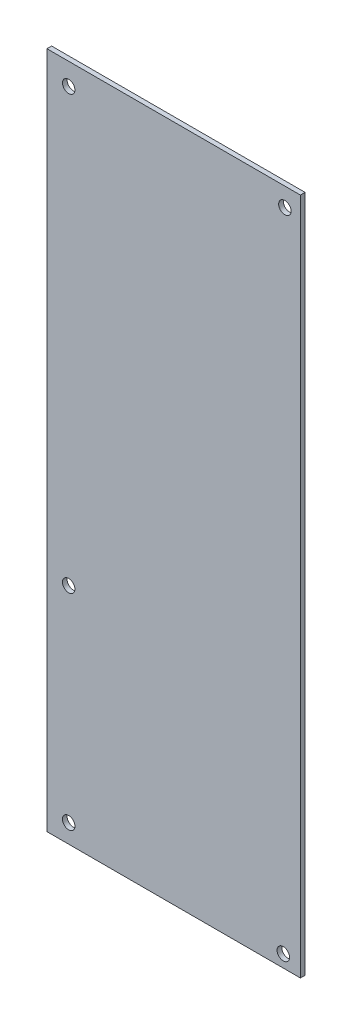
SolidWorks part; units mm, degrees
ref_plane "Plan de face" through (0, 0, 0) normal (0, 0, 1) x (1, 0, 0)
ref_plane "Plan de dessus" through (0, 0, 0) normal (0, 1, 0) x (1, 0, 0)
ref_plane "Plan de droite" through (0, 0, 0) normal (1, 0, 0) x (0, 0, -1)
sketch "Main-Sketch" plane through (0, 0, 0) normal (0, 0, 1) x (1, 0, 0)
  line L1 (0, 0) -> (81.5, 0)
  line L2 (0, 0) -> (0, 218)
  line L3 (0, 218) -> (81.5, 218)
  line L4 (81.5, 0) -> (81.5, 218)
  dimension "D1" = 81.5
  dimension "D2" = 218
extrude "Main" add sketch "Main-Sketch" along normal blind 1.5
sketch "Hole-Sketch" plane through (0, 0, 1.5) normal (0, 0, 1) x (1, 0, 0)
  line L0 (0, 0) -> (81.5, 0) construction
  line L1 (81.5, 0) -> (81.5, 218) construction
  line L2 (81.5, 218) -> (0, 218) construction
  line L3 (0, 218) -> (0, 0) construction
  circle A0 centre (7, 211) radius 2
  circle A1 centre (76.5, 212) radius 2
  circle A2 centre (7, 6) radius 2
  circle A3 centre (76, 4) radius 2
  circle A4 centre (7, 72) radius 2
  point P16 (0, 0)
  dimension "D1" = 4
  dimension "D3" = 4
  dimension "D4" = 4
  dimension "D2" = 4
  dimension "D5" = 5
  dimension "D6" = 6
  dimension "D7" = 7
  dimension "D8" = 7
  dimension "D9" = 7
  dimension "D10" = 6
  dimension "D11" = 5.5
  dimension "D12" = 72
extrude "Hole" cut sketch "Hole-Sketch" against normal through all
